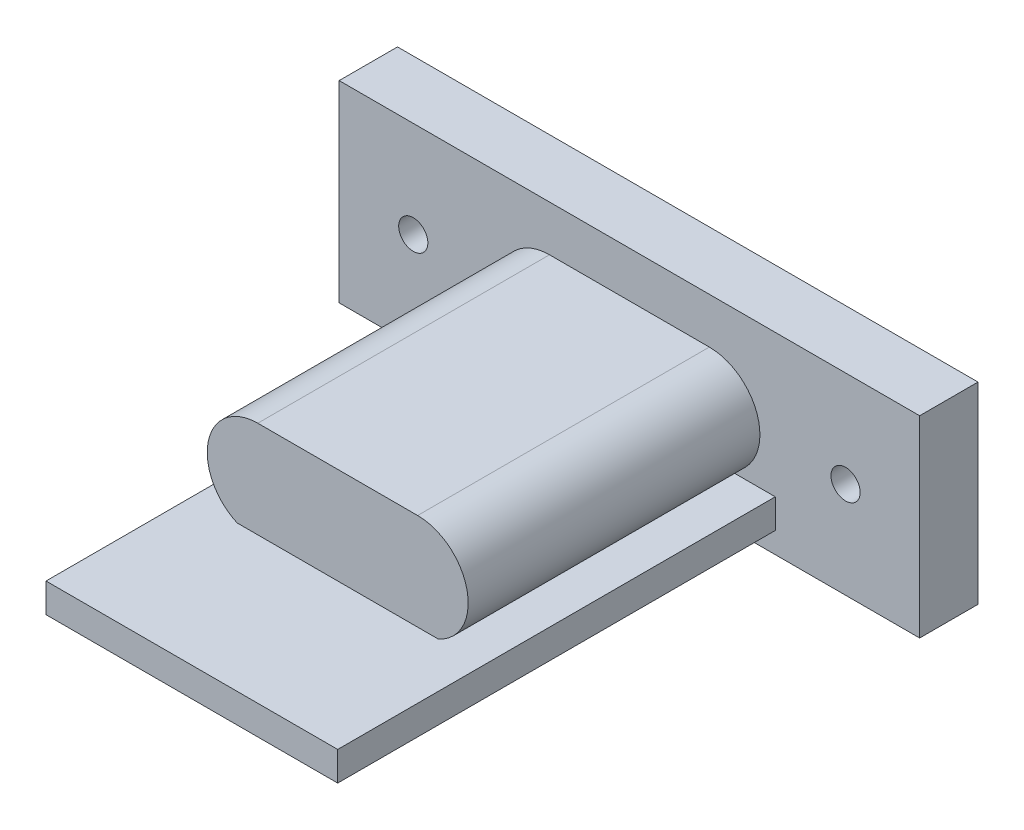
SolidWorks part; units mm, degrees
ref_plane "Front Plane" through (0, 0, 0) normal (0, 0, 1) x (1, 0, 0)
ref_plane "Top Plane" through (0, 0, 0) normal (0, 1, 0) x (1, 0, 0)
ref_plane "Right Plane" through (0, 0, 0) normal (1, 0, 0) x (0, 0, -1)
sketch "Sketch1" plane through (0, 0, 0) normal (0, 0, 1) x (1, 0, 0)
  line L0 (0, 3.3) -> (19.9, 3.3) construction
  line L1 (0, 0) -> (19.9, 0)
  line L2 (0, 0) -> (0, 6.6)
  line L3 (0, 6.6) -> (19.9, 6.6)
  line L4 (19.9, 0) -> (19.9, 6.6)
  line L5 (7.21, 3.3) -> (12.69, 3.3) construction
  line L6 (7.21, 4.88) -> (12.69, 4.88)
  line L7 (7.21, 1.72) -> (12.69, 1.72)
  circle A0 centre (2.54, 3.3) radius 0.5
  circle A1 centre (17.36, 3.3) radius 0.5
  arc A2 (7.21, 4.88) -> (7.21, 1.72) centre (7.21, 3.3) ccw
  arc A3 (12.69, 1.72) -> (12.69, 4.88) centre (12.69, 3.3) ccw
  point P11 (9.95, 3.3)
  point P18 (5.63, 3.3)
  point P19 (14.27, 3.3)
  point P20 (9.95, 3.3)
  dimension "D3" = 1
  dimension "D4" = 1
  dimension "D5" = 2.54
  dimension "D8" = 3.16
  dimension "D1" = 19.9
  dimension "D2" = 6.6
  dimension "D6" = 2.54
  dimension "D7" = 8.64
extrude "Boss-Extrude1" add sketch "Sketch1" along normal blind 2
sketch "Sketch6" plane through (0, 0, 2) normal (0, 0, 1) x (1, 0, 0)
  line L0 (7.21, 3.3) -> (12.69, 3.3) construction
  line L1 (7.21, 5.0331) -> (12.69, 5.0331)
  line L3 (7.21, 3.3) -> (12.69, 3.3) construction
  line L4 (7.21, 4.57) -> (12.69, 4.57)
  line L5 (7.21, 2.03) -> (12.69, 2.03)
  line L6 (0, 0) -> (19.9, 0) construction
  line L7 (4.95, 1.7181) -> (6.502, 1.7181)
  line L8 (4.95, 1.7181) -> (4.95, 0.7181)
  line L9 (4.95, 0.7181) -> (14.95, 0.7181)
  line L10 (14.95, 1.7181) -> (14.95, 0.7181)
  line L11 (13.398, 1.7181) -> (14.95, 1.7181)
  arc A0 (7.21, 5.0331) -> (6.502, 1.7181) centre (7.21, 3.3) ccw
  arc A1 (13.398, 1.7181) -> (12.69, 5.0331) centre (12.69, 3.3) ccw
  arc A2 (7.21, 4.57) -> (7.21, 2.03) centre (7.21, 3.3) ccw
  arc A3 (12.69, 2.03) -> (12.69, 4.57) centre (12.69, 3.3) ccw
  point P4 (9.95, 3.3)
  point P11 (9.95, 3.3)
  point P22 (9.95, 0)
  point P23 (9.95, 0.7181)
  dimension "D1" = 2.54
  dimension "D2" = 10
  dimension "D3" = 1
extrude "Boss-Extrude11" add sketch "Sketch6" along normal blind 10
sketch "Sketch7" plane through (0, 0, 12) normal (0, 0, 1) x (1, 0, 0)
  line L0 (7.21, 3.3) -> (12.69, 3.3) construction
  line L1 (7.21, 5.0331) -> (12.69, 5.0331)
  line L2 (7.21, 1.5669) -> (12.69, 1.5669)
  line L3 (12.69, 5.0331) -> (7.21, 5.0331) construction
  arc A0 (7.21, 5.0331) -> (7.21, 1.5669) centre (7.21, 3.3) ccw
  arc A1 (12.69, 1.5669) -> (12.69, 5.0331) centre (12.69, 3.3) ccw
  point P4 (9.95, 3.3)
extrude "Boss-Extrude12" add sketch "Sketch7" against normal blind 1
sketch "Sketch8" plane through (0, 0, 12) normal (0, 0, 1) x (1, 0, 0)
  line L1 (4.95, 1.7181) -> (14.95, 1.7181)
  line L2 (4.95, 1.7181) -> (4.95, 0.7181)
  line L3 (4.95, 0.7181) -> (14.95, 0.7181)
  line L4 (14.95, 1.7181) -> (14.95, 0.7181)
extrude "Boss-Extrude13" add sketch "Sketch8" along normal blind 5
